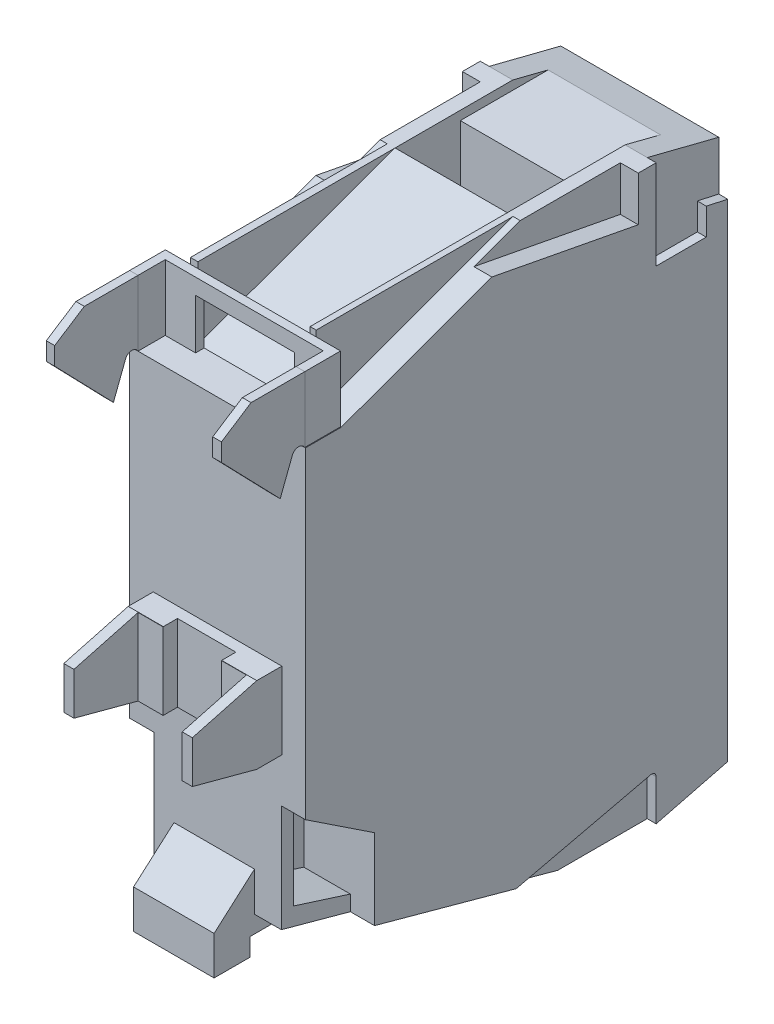
SolidWorks part; units mm, degrees
ref_plane "Front Plane" through (0, 0, 0) normal (0, 0, 1) x (1, 0, 0)
ref_plane "Top Plane" through (0, 0, 0) normal (0, 1, 0) x (1, 0, 0)
ref_plane "Right Plane" through (0, 0, 0) normal (1, 0, 0) x (0, 0, -1)
sketch "Sketch1" plane through (0, 0, 0) normal (0, 0, 1) x (1, 0, 0)
  line L0 (-4.915, -16) -> (4.915, 16) construction
  line L1 (-4.915, 16) -> (4.915, 16)
  line L2 (-4.915, 16) -> (-4.915, -16)
  line L3 (-4.915, -16) -> (4.915, -16)
  line L4 (4.915, 16) -> (4.915, -16)
  line L5 (0, 16) -> (0, -16) construction
  point P4 (0, 0)
  dimension "D1" = 9.83
  dimension "D2" = 32
extrude "Boss-Extrude1" add sketch "Sketch1" along normal blind 23.6
sketch "Sketch2" plane through (4.915, 0, 0) normal (1, 0, 0) x (0, 0, -1)
  line L0 (0, 14.9858) -> (-4, 14.9858) construction
  line L1 (0, -16) -> (0, 16) construction
  line L2 (-4, 16) -> (-4, 15) construction
  line L3 (-23.6, 16) -> (0, 16) construction
  line L4 (-4, 16) -> (0, 14.9858)
  line L5 (-4, 16) -> (0, 16)
  line L6 (0, 16) -> (0, 14.9858)
  line L7 (-23.6, 0) -> (0, 0) construction
  line L8 (-23.6, -16) -> (-23.6, 16) construction
  line L9 (-4, -16) -> (-4, -15) construction
  line L10 (0, -14.9858) -> (-4, -14.9858) construction
  line L11 (0, -16) -> (0, -14.9858)
  line L12 (-4, -16) -> (0, -16)
  line L13 (-4, -16) -> (0, -14.9858)
extrude "Cut-Extrude1" cut sketch "Sketch2" against normal up to next
sketch "Sketch3" plane through (4.915, 0, 0) normal (1, 0, 0) x (0, 0, -1)
  line L0 (-4, 16) -> (-4, 11)
  line L1 (-4, 11) -> (-1.2, 11)
  line L2 (-1.2, 11) -> (-1.2, 12.5)
  line L3 (-1.2, 12.5) -> (0, 12.2359)
  line L4 (0, -14.9858) -> (0, 14.9858) construction
  line L5 (0, 12.2359) -> (0, 14.9858)
  line L6 (0, 14.9858) -> (-4, 16)
sketch "Sketch5" plane through (-4.915, 0, 0) normal (-1, 0, 0) x (0, 0, 1)
  line L0 (4, 16) -> (4, 11)
  line L1 (4, 11) -> (1.2, 11)
  line L2 (1.2, 11) -> (1.2, 12.5)
  line L3 (1.2, 12.5) -> (0, 12.2359)
  line L4 (0, 12.2359) -> (0, 14.9858)
  line L5 (0, 14.9858) -> (4, 16)
extrude "Cut-Extrude2" cut sketch "Sketch5" against normal blind 0.5
extrude "Cut-Extrude3" cut sketch "Sketch3" against normal blind 0.5
sketch "Sketch6" plane through (4.915, 0, 0) normal (1, 0, 0) x (0, 0, -1)
  line L0 (-4, -16) -> (-9, -16) construction
  line L1 (-23.6, -16) -> (-4, -16) construction
  line L2 (-23.6, 16) -> (-23.6, -12) construction
  line L3 (-23.6, -16) -> (-23.6, 16) construction
  line L4 (-23.6, -12) -> (-9, -16)
  line L5 (-9, -16) -> (-23.6, -16)
  line L6 (-23.6, -16) -> (-23.6, -12)
extrude "Cut-Extrude4" cut sketch "Sketch6" against normal up to next
sketch "Sketch7" plane through (4.915, 0, 0) normal (1, 0, 0) x (0, 0, -1)
  line L0 (-23.6, 2) -> (0, 2) construction
  line L1 (-23.6, -12) -> (-23.6, 16) construction
  line L2 (0, -14.9858) -> (0, 12.2359) construction
  line L3 (-4, -16) -> (-4, -13.7152)
  line L4 (-4.3069, -13.4717) -> (-11.8196, -15.2275)
  line L5 (-9, -16) -> (-23.6, -12) construction
  line L6 (-11.8196, -15.2275) -> (-9, -16)
  line L7 (-9, -16) -> (-4, -16)
  arc A0 (-4, -13.7152) -> (-4.3069, -13.4717) centre (-4.25, -13.7152) ccw
  dimension "D1" = 0.25
extrude "Cut-Extrude5" cut sketch "Sketch7" against normal blind 0.5
sketch "Sketch8" plane through (-4.915, 0, 0) normal (-1, 0, 0) x (0, 0, 1)
  line L0 (4, -16) -> (4, -13.7152)
  line L1 (4, -13.7152) -> (4.0946, -13.5193)
  line L2 (4.0946, -13.5193) -> (4.3069, -13.4717)
  line L3 (4.3069, -13.4717) -> (11.8196, -15.2275)
  line L4 (11.8196, -15.2275) -> (9, -16)
  line L5 (9, -16) -> (4, -16)
  arc A0 (4.3069, -13.4717) -> (4, -13.7152) centre (4.25, -13.7152) ccw construction
extrude "Cut-Extrude6" cut sketch "Sketch8" against normal blind 0.5 contours L5 L0 L1 L2 L3 L4
sketch "Sketch9" plane through (4.915, 0, 0) normal (1, 0, 0) x (0, 0, -1)
  line L1 (-23.6, 16) -> (-21.6, 16)
  line L2 (-23.6, 16) -> (-23.6, 12)
  line L3 (-23.6, 12) -> (-21.6, 12)
  line L4 (-21.6, 16) -> (-21.6, 12)
extrude "Cut-Extrude7" cut sketch "Sketch9" against normal up to next
sketch "Sketch10" plane through (4.915, 0, 0) normal (1, 0, 0) x (0, 0, -1)
  line L0 (-5, 13.5) -> (-4, 13.5) construction
  line L1 (-4, 16) -> (-4, 11) construction
  line L2 (-5, 13.5) -> (-5, 16)
  line L3 (-21.6, 16) -> (-4, 16) construction
  line L4 (-5, 13.5) -> (-18.1024, 16)
  line L5 (-18.1024, 16) -> (-5, 16)
extrude "Cut-Extrude8" cut sketch "Sketch10" against normal blind 1
sketch "Sketch11" plane through (4.915, 0, 0) normal (1, 0, 0) x (0, 0, -1)
  line L0 (-21.6, 16) -> (-10.6, 16)
  line L1 (-10.6, 16) -> (-21.6, 12)
  line L2 (-21.6, 12) -> (-21.6, 16)
extrude "Cut-Extrude9" cut sketch "Sketch11" against normal blind 1.4
sketch "Sketch12" plane through (-4.915, 0, 0) normal (-1, 0, 0) x (0, 0, 1)
  line L0 (5, 16) -> (5, 13.5)
  line L1 (5, 13.5) -> (18.1024, 16)
  line L2 (18.1024, 16) -> (5, 16)
extrude "Cut-Extrude10" cut sketch "Sketch12" against normal blind 1 contours L2 L0 L1
sketch "Sketch13" plane through (-4.915, 0, 0) normal (-1, 0, 0) x (0, 0, 1)
  line L0 (21.6, 12) -> (21.6, 16)
  line L1 (21.6, 16) -> (10.6, 16)
  line L2 (10.6, 16) -> (21.6, 12)
extrude "Cut-Extrude11" cut sketch "Sketch13" against normal blind 1.4
sketch "Sketch14" plane through (4.915, 0, 0) normal (1, 0, 0) x (0, 0, -1)
  line L0 (-23.6, -12) -> (-23.6, -6)
  line L1 (-23.6, -12) -> (-23.6, 12) construction
  line L2 (-23.6, -12) -> (-19.7422, -13.0569)
  line L3 (-11.8196, -15.2275) -> (-23.6, -12) construction
  line L4 (-19.7422, -13.0569) -> (-19.7422, -8.5569)
  line L5 (-19.7422, -8.5569) -> (-23.6, -6)
extrude "Cut-Extrude12" cut sketch "Sketch14" against normal blind 1.35
sketch "Sketch15" plane through (-4.915, 0, 0) normal (-1, 0, 0) x (0, 0, 1)
  line L0 (19.7422, -13.0569) -> (19.7422, -8.5569)
  line L1 (19.7422, -8.5569) -> (23.6, -6)
  line L2 (23.6, -6) -> (23.6, -12)
  line L3 (23.6, -12) -> (19.7422, -13.0569)
extrude "Cut-Extrude13" cut sketch "Sketch15" against normal blind 1.35
sketch "Sketch16" plane through (3.565, 0, 0) normal (1, 0, 0) x (0, 0, -1)
  line L0 (-22.9226, -6.449) -> (-22.9226, -11.1904)
  line L1 (-19.7422, -8.5569) -> (-23.6, -6) construction
  line L2 (-22.9226, -11.1904) -> (-19.7422, -12.2011)
  line L3 (-19.7422, -13.0569) -> (-19.7422, -8.5569) construction
  line L4 (-22.9226, -6.449) -> (-19.7422, -8.5569)
  line L5 (-19.7422, -8.5569) -> (-19.7422, -12.2011)
extrude "Cut-Extrude14" cut sketch "Sketch16" against normal blind 2.6
sketch "Sketch18" plane through (-3.565, 0, 0) normal (-1, 0, 0) x (0, 0, 1)
  line L0 (19.7422, -12.2011) -> (19.7422, -8.5569)
  line L1 (19.7422, -8.5569) -> (22.9226, -6.449)
  line L2 (22.9226, -6.449) -> (22.9226, -11.1904)
  line L3 (22.9226, -11.1904) -> (19.7422, -12.2011)
extrude "Cut-Extrude15" cut sketch "Sketch18" against normal blind 3.6
sketch "Sketch19" plane through (0, -14.0807, -3.5701) normal (0, -0.9693, -0.2458) x (1, 0, 0)
  line L1 (3.7246, 7.1036) -> (-3.4583, 7.1036)
  line L2 (3.7246, 7.1036) -> (3.7246, 4.9248)
  line L3 (3.7246, 4.9248) -> (-3.4583, 4.9248)
  line L4 (-3.4583, 7.1036) -> (-3.4583, 4.9248)
extrude "Cut-Extrude18" cut sketch "Sketch19" against normal blind 1.32
chamfer "Chamfer2" distance 0.75 angle 75 3 edges at (-3.4583, -15.5588, 2.2597) (0.1332, -15.291, 1.2037) (3.7246, -15.5588, 2.2597)
sketch "Sketch21" plane through (0, -14.0807, -3.5701) normal (0, -0.9693, -0.2458) x (-1, 0, 0)
  line L1 (-4.0773, -7.1036) -> (4.2083, -7.1036)
  line L2 (-4.0773, -7.1036) -> (-4.0773, -12.5673)
  line L3 (-4.0773, -12.5673) -> (4.2083, -12.5673)
  line L4 (4.2083, -7.1036) -> (4.2083, -12.5673)
extrude "Cut-Extrude19" cut sketch "Sketch21" against normal blind 4.25
sketch3d "3DSketch1" plane through (0, 0, 0) normal (0, 0, 1) x (1, 0, 0)
  dimension "D1" = 3.75
sketch "Sketch22" plane through (-0.185, 0, 0) normal (1, 0, 0) x (0, 0, -1)
  line L0 (-19.8581, -12.9572) -> (-23.8581, -12.9572)
  line L1 (-23.8581, -12.9572) -> (-23.8581, -13.9572)
  line L2 (-23.8581, -13.9572) -> (-25.8581, -13.9572)
  line L3 (-25.8581, -13.9572) -> (-25.8581, -11.7988)
  line L4 (-25.8581, -11.7988) -> (-23.5927, -9.8081)
  line L5 (-23.5927, -9.8081) -> (-23.4731, -11.3744)
  line L6 (-23.4731, -11.3744) -> (-19.8581, -12.9572)
extrude "Boss-Extrude2" add sketch "Sketch22" against normal blind 2.25 and the other way blind 2.25
sketch "Sketch23" plane through (0, 16, 0) normal (0, 1, 0) x (1, 0, 0)
  line L1 (-3.0982, -6.933) -> (3.1743, -6.933)
  line L2 (-3.0982, -6.933) -> (-3.0982, -21.6)
  line L3 (-3.0982, -21.6) -> (3.1743, -21.6)
  line L4 (3.1743, -6.933) -> (3.1743, -21.6)
  line L5 (-3.515, -21.6) -> (3.515, -21.6) construction
extrude "Cut-Extrude20" cut sketch "Sketch23" against normal up to vertex (4 mm away)
sketch "Sketch24" plane through (3.1743, 0, 0) normal (-1, 0, 0) x (0, 0, 1)
  line L0 (10.5797, 16) -> (21.6, 12)
  line L1 (21.6, 16) -> (6.933, 16) construction
  line L2 (21.6, 12) -> (10.5797, 12)
  line L3 (21.6, 12) -> (6.933, 12) construction
  line L4 (10.5797, 12) -> (10.5797, 16)
extrude "Boss-Extrude3" add sketch "Sketch24" along normal up to next
sketch "Sketch25" plane through (0, 16, 0) normal (0, 1, 0) x (1, 0, 0)
  line L1 (-3.0982, -6.933) -> (3.1814, -6.933)
  line L2 (-3.0982, -6.933) -> (-3.0982, -0.7769)
  line L3 (-3.0982, -0.7769) -> (3.1814, -0.7769)
  line L4 (3.1814, -6.933) -> (3.1814, -0.7769)
extrude "Cut-Extrude21" cut sketch "Sketch25" against normal blind 0.5
sketch "Sketch26" plane through (0, 0, 0) normal (0, 0, -1) x (-1, 0, 0)
  line L0 (-4.915, -1.375) -> (4.915, -1.375) construction
  line L3 (-3.5929, -3.5227) -> (3.5929, 0.7728) construction
  line L4 (-3.5929, 0.7728) -> (3.5929, 0.7728)
  line L5 (-3.5929, 0.7728) -> (-3.5929, -3.5227)
  line L6 (-3.5929, -3.5227) -> (3.5929, -3.5227)
  line L7 (3.5929, 0.7728) -> (3.5929, -3.5227)
  line L8 (4.915, 12.2359) -> (4.915, -14.9858) construction
  line L9 (-4.915, -14.9858) -> (-4.915, 12.2359) construction
  point P10 (0, -1.375)
  point P11 (0, -1.375)
  dimension "D1" = 7.1858
extrude "Cut-Extrude22" cut sketch "Sketch26" against normal through all
sketch "Sketch27" plane through (0, 0, 23.6) normal (0, 0, 1) x (1, 0, 0)
  line L1 (-3.5929, 0.7728) -> (3.5929, 0.7728)
  line L2 (-3.5929, 0.7728) -> (-3.5929, -3.5227)
  line L3 (-3.5929, -3.5227) -> (3.5929, -3.5227)
  line L4 (3.5929, 0.7728) -> (3.5929, -3.5227)
extrude "Boss-Extrude4" add sketch "Sketch27" along normal blind 5 and the other way blind 19.5 separate body
sketch "Sketch28" plane through (0, 0.7728, 0) normal (0, 1, 0) x (1, 0, 0)
  line L0 (3.0249, -28.6) -> (3.0249, -25.0138)
  line L1 (3.5929, -28.6) -> (-3.5929, -28.6) construction
  line L2 (3.0249, -25.0138) -> (1.6314, -25.0138)
  line L3 (1.6314, -25.0138) -> (1.6314, -24.2085)
  line L4 (1.6314, -24.2085) -> (-1.6314, -24.2085)
  line L5 (0, -24.2085) -> (0, -23.6)
  line L6 (3.5929, -23.6) -> (-3.5929, -23.6) construction
  line L7 (-3.5929, -23.6) -> (3.5929, -23.6)
  line L8 (3.5929, -23.6) -> (3.5929, -28.6)
  line L9 (3.5929, -28.6) -> (3.0249, -28.6)
  line L10 (0, -23.6) -> (0, -28.6) construction
  line L11 (-3.5929, -28.6) -> (-3.0249, -28.6)
  line L12 (-3.5929, -23.6) -> (-3.5929, -28.6)
  line L13 (-1.6314, -25.0138) -> (-1.6314, -24.2085)
  line L14 (-3.0249, -25.0138) -> (-1.6314, -25.0138)
  line L15 (-3.0249, -28.6) -> (-3.0249, -25.0138)
  line M11 (-3.5929, -28.6) -> (3.5929, -28.6)
extrude "Cut-Extrude23" cut sketch "Sketch28" against normal up to next (4.2956 mm away) contours L10 L4 L13 L14 L15 M11 | L4 L10 L0 L2 L3 M11
chamfer "Chamfer3" distance 3.6 angle 15 2 edges at (3.3089, 0.7728, 28.6) (3.3089, -3.5227, 28.6)
chamfer "Chamfer4" distance 3.6 angle 15 2 edges at (-3.3089, 0.7728, 28.6) (-3.3089, -3.5227, 28.6)
sketch "Sketch29" plane through (0, 0, 4.1) normal (0, 0, -1) x (-1, 0, 0)
  line L0 (3.5929, -3.5227) -> (-3.5929, -3.5227) construction
  line L1 (-1.7574, 0.6607) -> (1.7416, 0.6607)
  line L2 (-1.7574, 0.6607) -> (-1.7574, -3.5227)
  line L3 (-1.7574, -3.5227) -> (1.7416, -3.5227)
  line L4 (1.7416, 0.6607) -> (1.7416, -3.5227)
extrude "Boss-Extrude5" add sketch "Sketch29" along normal blind 0.25
sketch "Sketch30" plane through (0, 0, 0) normal (0, 0, -1) x (-1, 0, 0)
  line L1 (-4.3873, 11.3819) -> (4.2265, 11.3819)
  line L2 (-4.3873, 11.3819) -> (-4.3873, 7.8691)
  line L3 (-4.3873, 7.8691) -> (4.2265, 7.8691)
  line L4 (4.2265, 11.3819) -> (4.2265, 7.8691)
  circle A0 centre (0, 9.6814) radius 2.75
  circle A1 centre (0, -10.2363) radius 2.75
extrude "Cut-Extrude24" cut sketch "Sketch30" against normal blind 4 contours A0 L3 L4 L1 | L1 A0 L3 | L1 A0 | A1
sketch "Sketch31" plane through (0, 0, 4) normal (0, 0, -1) x (-1, 0, 0)
  line L0 (0, 12.4314) -> (0, 6.9314) construction
  line L1 (0, -10.2363) -> (0, -7.4863) construction
  arc A1 (2.1613, 11.3819) -> (-2.1613, 11.3819) centre (0, 9.6814) ccw construction
  arc A2 (-2.0683, 7.8691) -> (2.0683, 7.8691) centre (0, 9.6814) ccw construction
  circle A3 centre (0, -10.2363) radius 2.75 construction
  circle A4 centre (0, 9.6814) radius 2.75
  circle A5 centre (0, -10.2363) radius 2.75
extrude "Cut-Extrude25" cut sketch "Sketch31" against normal blind 1
sketch "Sketch32" plane through (0, 0, 5) normal (0, 0, -1) x (-1, 0, 0)
  line L0 (0, 12.4314) -> (0, 9.6814) construction
  line L1 (0, 9.6814) -> (0, -7.4863) construction
  line L2 (0, -7.4863) -> (0, -10.2363) construction
  circle A0 centre (0, 9.6814) radius 2.75 construction
  arc A1 (2.2128, -11.8691) -> (-2.2128, -11.8691) centre (0, -10.2363) ccw construction
  circle A2 centre (0, 9.6814) radius 2.75
  circle A3 centre (0, -10.2363) radius 2.75
extrude "Boss-Extrude6" add sketch "Sketch32" along normal blind 0.75 separate body
sketch "Sketch33" plane through (0, 0, 4.25) normal (0, 0, -1) x (-1, 0, 0)
  line L0 (0, 9.6814) -> (0, -10.2363) construction
  line L1 (0, -0.2774) -> (-5.7173, -0.2774) construction
  line L2 (-1.4585, 9.3898) -> (1.4585, 9.9731) construction
  line L3 (-0.3233, 11.8782) -> (0.299, 11.8782)
  line L4 (-0.3233, 11.8782) -> (-0.3233, 7.392)
  line L5 (-0.3233, 7.392) -> (0.299, 7.392)
  line L6 (0.299, 11.8782) -> (0.299, 7.392)
  line L7 (-1.4585, 9.9731) -> (1.4585, 9.9731)
  line L8 (-1.4585, 9.9731) -> (-1.4585, 9.3898)
  line L9 (-1.4585, 9.3898) -> (1.4585, 9.3898)
  line L10 (1.4585, 9.9731) -> (1.4585, 9.3898)
  line L11 (-1.4585, -9.9447) -> (1.4585, -10.5279) construction
  line L12 (1.4585, -10.5279) -> (1.4585, -9.9447)
  line L13 (-1.4585, -9.9447) -> (1.4585, -9.9447)
  line L14 (-1.4585, -10.5279) -> (-1.4585, -9.9447)
  line L15 (-1.4585, -10.5279) -> (1.4585, -10.5279)
  line L16 (0.299, -12.4331) -> (0.299, -7.9469)
  line L17 (-0.3233, -7.9469) -> (0.299, -7.9469)
  line L18 (-0.3233, -12.4331) -> (-0.3233, -7.9469)
  line L19 (-0.3233, -12.4331) -> (0.299, -12.4331)
  point P11 (0, 9.6814)
  circle M7 centre (0, 9.6814) radius 2.75
extrude "Cut-Extrude26" cut sketch "Sketch33" against normal blind 0.75 contours L4 L7 L6 L3 | L10 L7 L6 L9 | L9 L4 L5 L6 M7 | L4 L9 L6 L7 | L8 L9 L4 L7 | L18 L13 L16 L17 | L18 L15 L16 L13 | L18 L19 L16 L15
sketch "Sketch35" plane through (0, 0, 21.6) normal (0, 0, 1) x (1, 0, 0)
  line L1 (-4.915, 12) -> (4.8761, 12)
  line L2 (-4.915, 12) -> (-4.915, 15.6698)
  line L3 (-4.915, 15.6698) -> (4.8761, 15.6698)
  line L4 (4.8761, 12) -> (4.8761, 15.6698)
extrude "Boss-Extrude8" add sketch "Sketch35" along normal up to vertex (2 mm away) separate body
sketch "Sketch37" plane through (-4.915, 0, 0) normal (-1, 0, 0) x (0, 0, 1)
  line L0 (23.6, 15.6698) -> (26.6, 15.6698)
  line L1 (26.6, 15.6698) -> (28.2571, 14.5987)
  line L2 (28.2571, 14.5987) -> (28.2571, 13.5987)
  line L3 (28.2571, 13.5987) -> (24.9738, 10.2049)
  line L4 (24.9738, 10.2049) -> (24.2822, 12.0004)
  line L5 (23.6, 15.6698) -> (23.6, 12)
  arc A0 (24.2822, 12.0004) -> (23.6, 12) centre (23.9412, 11.8237) ccw
extrude "Boss-Extrude9" add sketch "Sketch37" against normal up to vertex (9.7911 mm away) separate body
sketch "Sketch38" plane through (0, 15.6698, 0) normal (0, 1, 0) x (1, 0, 0)
  line L1 (-4.4453, -22.0771) -> (4.3869, -22.0771)
  line L2 (-4.4453, -22.0771) -> (-4.4453, -30.1169)
  line L3 (-4.4453, -30.1169) -> (4.3869, -30.1169)
  line L4 (4.3869, -22.0771) -> (4.3869, -30.1169)
extrude "Cut-Extrude32" cut sketch "Sketch38" against normal up to vertex (3.6698 mm away)
sketch "Sketch41" plane through (0, 12, 0) normal (0, 1, 0) x (1, 0, 0)
  line L1 (-4.4453, -24.2823) -> (4.3869, -24.2823)
  line L2 (-4.4453, -24.2823) -> (-4.4453, -26.7105)
  line L3 (-4.4453, -26.7105) -> (4.3869, -26.7105)
  line L4 (4.3869, -24.2823) -> (4.3869, -26.7105)
extrude "Cut-Extrude33" cut sketch "Sketch41" against normal up to next
sketch "Sketch42" plane through (0, 0, 22.0771) normal (0, 0, 1) x (1, 0, 0)
  line L0 (4.3869, 12) -> (-4.4453, 12) construction
  line L1 (-2.7506, 12) -> (2.7661, 12)
  line L2 (-2.7506, 12) -> (-2.7506, 14.7886)
  line L3 (-2.7506, 14.7886) -> (2.7661, 14.7886)
  line L4 (2.7661, 12) -> (2.7661, 14.7886)
extrude "Cut-Extrude34" cut sketch "Sketch42" against normal up to next
sketch "Sketch43" plane through (0, 0, 0) normal (0, 0, -1) x (-1, 0, 0)
  text T0 "NO" font "Century Gothic" height in points 8
  text T1 "3"
  text T2 "4"
extrude "Cut-Extrude35" cut sketch "Sketch43" against normal blind 0.01
